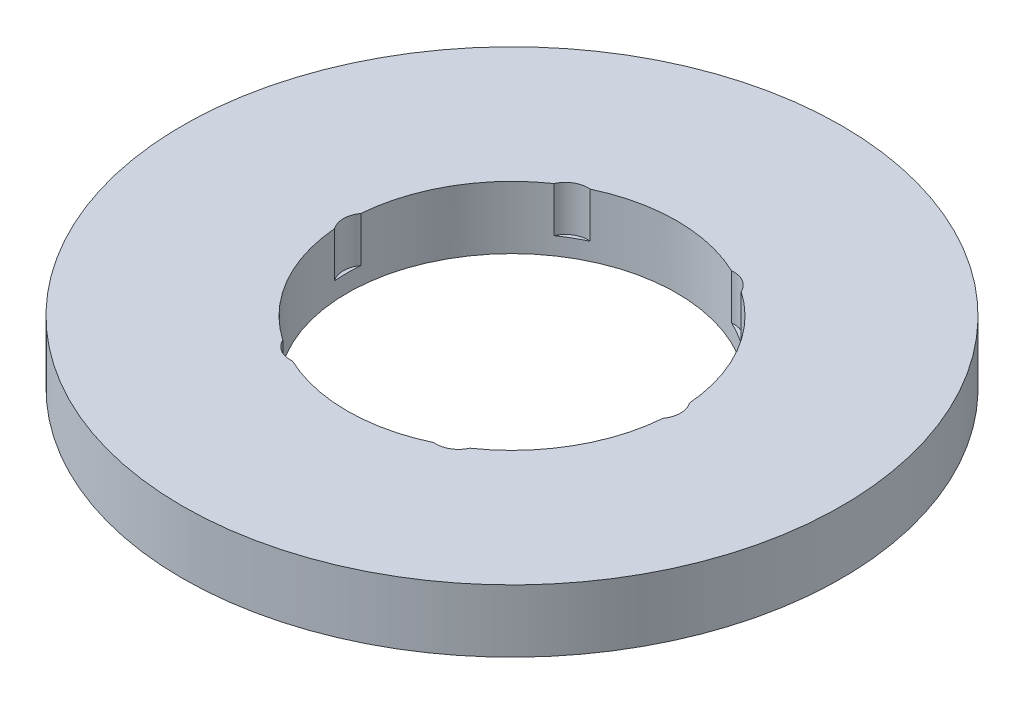
SolidWorks part; units mm, degrees
ref_plane "Front Plane" through (0, 0, 0) normal (0, 0, 1) x (1, 0, 0)
ref_plane "Top Plane" through (0, 0, 0) normal (0, 1, 0) x (1, 0, 0)
ref_plane "Right Plane" through (0, 0, 0) normal (1, 0, 0) x (0, 0, -1)
sketch "Sketch1" plane through (0, 0, 0) normal (0, 1, 0) x (1, 0, 0)
  circle A0 centre (0, 0) radius 100
  dimension "FLANGE_OD" = 200
extrude "Boss-Extrude1" add sketch "Sketch1" along normal blind 19
sketch "Sketch2" plane through (0, 0, 0) normal (0, 1, 0) x (1, 0, 0)
  circle A0 centre (0, 0) radius 50
  dimension "BORE_D" = 100
extrude "Cut-Extrude1" cut sketch "Sketch2" along normal through all
sketch "Sketch3" plane through (0, 19, 0) normal (0, 1, 0) x (1, 0, 0)
  circle A0 centre (0, 0) radius 44.3186 construction
  circle A1 centre (-44.3186, 0) radius 6.8125
  dimension "BOLT_D" = 13.6249
  dimension "BOLT_PCD" = 88.6373
extrude "Cut-Extrude2" cut sketch "Sketch3" against normal blind 13.6981
pattern_circular "CirPattern1" count 6 over 360 about axis through (0, 0, 0) along (0, 1, 0) of "Cut-Extrude2"
